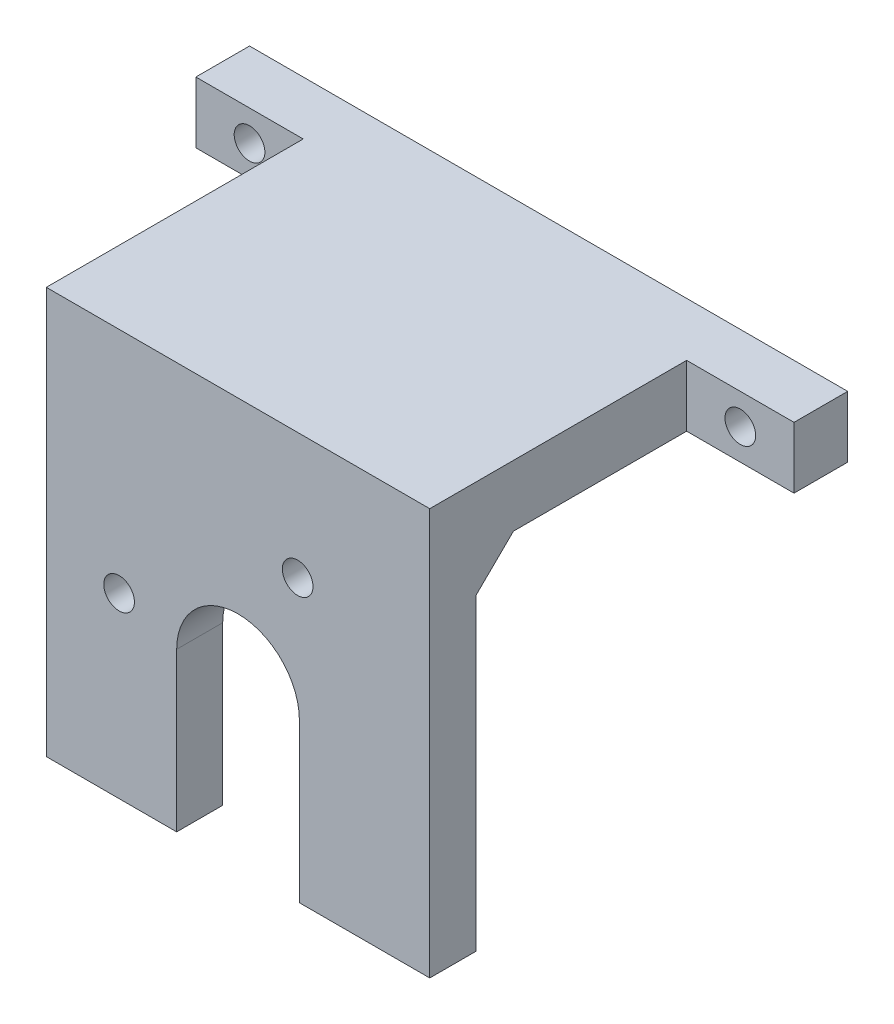
SolidWorks part; units mm, degrees
material "ABS"
ref_plane "Front Plane" through (0, 0, 0) normal (0, 0, 1) x (1, 0, 0)
ref_plane "Top Plane" through (0, 0, 0) normal (0, 1, 0) x (1, 0, 0)
ref_plane "Right Plane" through (0, 0, 0) normal (1, 0, 0) x (0, 0, -1)
sketch "Sketch1" plane through (0, 0, 0) normal (0, 0, 1) x (1, 0, 0)
  line L1 (-37.3941, 10.9555) -> (12.6059, 10.9555)
  line L2 (-37.3941, 10.9555) -> (-37.3941, -7.0445)
  line L3 (-37.3941, -7.0445) -> (12.6059, -7.0445)
  line L4 (12.6059, 10.9555) -> (12.6059, -7.0445)
  dimension "D1" = 50
  dimension "D2" = 18
extrude "Boss-Extrude1" add sketch "Sketch1" along normal blind 7
sketch "Sketch2" plane through (0, 0, 7) normal (0, 0, 1) x (1, 0, 0)
  line L0 (12.6059, -7.0445) -> (12.6059, 10.9555) construction
  line L1 (-37.3941, 10.9555) -> (12.6059, 10.9555)
  line L2 (-37.3941, 10.9555) -> (-37.3941, 2.9555)
  line L3 (-37.3941, 2.9555) -> (12.6059, 2.9555)
  line L4 (12.6059, 10.9555) -> (12.6059, 2.9555)
  dimension "D1" = 8
extrude "Boss-Extrude2" add sketch "Sketch2" along normal blind 33.5
sketch "Sketch3" plane through (12.6059, 0, 0) normal (1, 0, 0) x (0, 0, -1)
  line L0 (-40.5, 10.9555) -> (0, 10.9555) construction
  line L1 (-7, 2.9555) -> (0, 2.9555)
  line L2 (-7, 2.9555) -> (-7, 10.9555)
  line L3 (-7, 10.9555) -> (0, 10.9555)
  line L4 (0, 2.9555) -> (0, 10.9555)
extrude "Boss-Extrude3" add sketch "Sketch3" along normal blind 14
sketch "Sketch4" plane through (-37.3941, 0, 0) normal (-1, 0, 0) x (0, 0, 1)
  line L1 (7, 2.9555) -> (0, 2.9555)
  line L2 (7, 2.9555) -> (7, 10.9555)
  line L3 (7, 10.9555) -> (0, 10.9555)
  line L4 (0, 2.9555) -> (0, 10.9555)
extrude "Boss-Extrude4" add sketch "Sketch4" along normal blind 14
sketch "Sketch5" plane through (0, 0, 7) normal (0, 0, 1) x (1, 0, 0)
  line L1 (-37.3941, -7.0445) -> (12.6059, -7.0445)
  line L2 (-37.3941, -7.0445) -> (-37.3941, 2.9555)
  line L3 (-37.3941, 2.9555) -> (12.6059, 2.9555)
  line L4 (12.6059, -7.0445) -> (12.6059, 2.9555)
extrude "Cut-Extrude1" cut sketch "Sketch5" against normal blind 14
sketch "Sketch6" plane through (0, 0, 7) normal (0, 0, 1) x (1, 0, 0)
  line L0 (26.6059, 10.9555) -> (26.6059, 2.9555) construction
  line L1 (-51.3941, 2.9555) -> (-51.3941, 10.9555) construction
  line L2 (-51.3941, 2.9555) -> (-37.3941, 2.9555) construction
  line L3 (26.6059, 2.9555) -> (12.6059, 2.9555) construction
  circle A0 centre (-44.3941, 6.9555) radius 2
  circle A1 centre (19.6059, 6.9555) radius 2
  dimension "D1" = 4
  dimension "D2" = 4
  dimension "D3" = 7
  dimension "D4" = 7
  dimension "D5" = 4
  dimension "D6" = 4
extrude "Cut-Extrude2" cut sketch "Sketch6" against normal blind 14
sketch "Sketch7" plane through (0, 2.9555, 0) normal (0, -1, 0) x (1, 0, 0)
  line L0 (12.6059, 40.5) -> (12.6059, 7) construction
  line L1 (-37.3941, 40.5) -> (12.6059, 40.5)
  line L2 (-37.3941, 40.5) -> (-37.3941, 34.5)
  line L3 (-37.3941, 34.5) -> (12.6059, 34.5)
  line L4 (12.6059, 40.5) -> (12.6059, 34.5)
  dimension "D1" = 6
extrude "Boss-Extrude5" add sketch "Sketch7" along normal blind 45
sketch "Sketch8" plane through (0, 0, 40.5) normal (0, 0, 1) x (1, 0, 0)
  line L0 (-12.3941, -21.4212) -> (-12.3941, -42.0445) construction
  line L1 (12.6059, -42.0445) -> (-37.3941, -42.0445) construction
  line L2 (-4.3941, -21.4212) -> (-4.3941, -42.0445)
  line L3 (-20.3941, -21.4212) -> (-20.3941, -42.0445)
  line L4 (-37.3941, 10.9555) -> (-37.3941, -42.0445) construction
  arc A0 (-4.3941, -21.4212) -> (-20.3941, -21.4212) centre (-12.3941, -21.4212) ccw
  arc A1 (-20.3941, -42.0445) -> (-4.3941, -42.0445) centre (-12.3941, -42.0445) ccw
  point P4 (-12.3941, -31.7328)
  dimension "D1" = 16
  dimension "D2" = 25
extrude "Cut-Extrude3" cut sketch "Sketch8" against normal blind 35
sketch "Sketch9" plane through (0, 0, 34.5) normal (0, 0, -1) x (-1, 0, 0)
  circle A0 centre (27.901, -18.8469) radius 2
  circle A1 centre (4.6167, -5.4607) radius 2
  dimension "D1" = 4
  dimension "D2" = 4
extrude "Cut-Extrude5" cut sketch "Sketch9" against normal blind 35
sketch "Sketch12" plane through (-37.3941, 0, 0) normal (-1, 0, 0) x (0, 0, 1)
  line L0 (34.5, -1.8735) -> (29.5873, 2.9555)
  line L1 (34.5, -42.0445) -> (34.5, 2.9555) construction
  line L2 (34.5, 2.9555) -> (7, 2.9555) construction
  line L3 (29.5873, 2.9555) -> (34.5, 2.9555)
  line L4 (34.5, 2.9555) -> (34.5, -1.8735)
  point P6 (34.5, -1.8735)
  point P9 (29.5873, 2.9555)
extrude "Boss-Extrude8" add sketch "Sketch12" against normal blind 50
